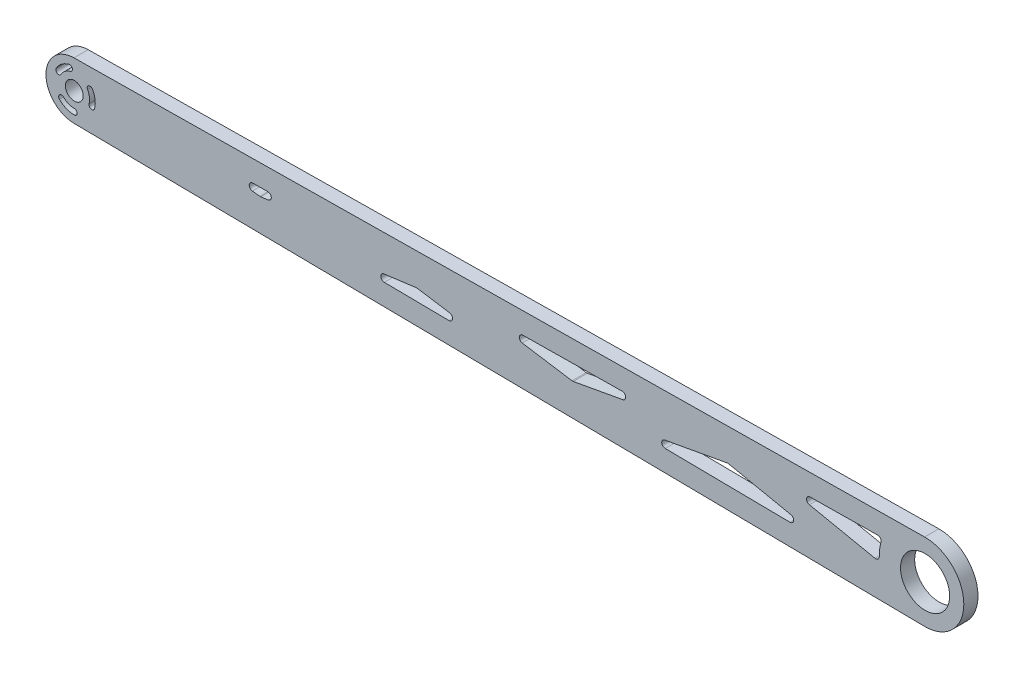
SolidWorks part; units mm, degrees
ref_plane "Front Plane" through (0, 0, 0) normal (0, 0, 1) x (1, 0, 0)
ref_plane "Top Plane" through (0, 0, 0) normal (0, 1, 0) x (1, 0, 0)
ref_plane "Right Plane" through (0, 0, 0) normal (1, 0, 0) x (0, 0, -1)
sketch "Sketch1" plane through (0, 0, 0) normal (0, 0, 1) x (1, 0, 0)
  line L0 (0, 0) -> (381, 0) construction
  line L4 (-0.155, 12.6991) -> (380.7882, 17.3487)
  line L5 (-0.155, -12.6991) -> (380.7882, -17.3487)
  circle A0 centre (0, 0) radius 4
  arc A1 (-0.155, 12.6991) -> (-0.155, -12.6991) centre (0, 0) ccw
  circle A2 centre (0, 0) radius 12.7 construction
  arc A5 (380.7882, -17.3487) -> (380.7882, 17.3487) centre (381, 0) ccw
  circle A6 centre (381, 0) radius 11
  dimension "D1" = 8
  dimension "D2" = 12.7
  dimension "D6" = 22
  dimension "D7" = 6.35
  dimension "D5" = 381
extrude "Boss-Extrude1" add sketch "Sketch1" along normal blind 6.35 contours A1 A5 A0 region at (198.4687, 0, 0)
sketch "Sketch2" plane through (0, 0, 6.35) normal (0, 0, 1) x (1, 0, 0)
  line L4 (13.1073, 3.3352) -> (83.3647, -4.1928) construction
  line L5 (13.6147, 8.0706) -> (83.8721, 0.5426)
  line L6 (-0.0387, -3.1748) -> (380.9045, -7.8244)
  line L7 (380.9045, 7.8244) -> (-0.0388, 3.1748)
  line L8 (-0.0387, -3.1748) -> (380.9045, -7.8244)
  line L9 (380.9045, 7.8244) -> (-0.0388, 3.1748)
  line L10 (12.5999, -1.4002) -> (82.8573, -8.9282)
  line L11 (83.3647, -4.1928) -> (153.4175, 5.0478) construction
  line L12 (82.7419, 0.5288) -> (152.7947, 9.7694)
  line L13 (83.9876, -8.9144) -> (154.0403, 0.3262)
  line L14 (153.4175, 5.0478) -> (223.2238, -5.8998) construction
  line L15 (154.1554, 9.7528) -> (223.9617, -1.1948)
  line L16 (152.6796, 0.3428) -> (222.4859, -10.6048)
  line L17 (223.2238, -5.8998) -> (292.7421, 6.7483) construction
  line L18 (222.3713, -1.2142) -> (291.8897, 11.4339)
  line L19 (224.0763, -10.5854) -> (293.5946, 2.0628)
  line L20 (292.7421, 6.7483) -> (361.9311, -7.5928) construction
  line L21 (293.7088, 11.4117) -> (362.8977, -2.9295)
  line L22 (291.7755, 2.085) -> (360.9645, -12.2562)
  circle A5 centre (381, 0) radius 11 construction
  arc A6 (380.9045, -7.8244) -> (380.9045, 7.8244) centre (381, 0) ccw
  arc A7 (-0.0388, 3.1748) -> (-0.0387, -3.1748) centre (0, 0) ccw
  arc A8 (380.9045, -7.8244) -> (380.9045, 7.8244) centre (381, 0) ccw
  arc A9 (-0.0388, 3.1748) -> (-0.0387, -3.1748) centre (0, 0) ccw
  circle A10 centre (0, 0) radius 13.525
  circle A11 centre (0, 0) radius 13.525
  circle A12 centre (381, 0) radius 11 construction
  circle A13 centre (381, 0) radius 20.525
  arc A14 (13.6147, 8.0706) -> (12.5999, -1.4002) centre (13.1073, 3.3352) ccw
  arc A15 (82.8573, -8.9282) -> (83.8721, 0.5426) centre (83.3647, -4.1928) ccw
  arc A16 (82.7419, 0.5288) -> (83.9876, -8.9144) centre (83.3647, -4.1928) ccw
  arc A17 (154.0403, 0.3262) -> (152.7947, 9.7694) centre (153.4175, 5.0478) ccw
  arc A18 (154.1554, 9.7528) -> (152.6796, 0.3428) centre (153.4175, 5.0478) ccw
  arc A19 (222.4859, -10.6048) -> (223.9617, -1.1948) centre (223.2238, -5.8998) ccw
  arc A20 (222.3713, -1.2142) -> (224.0763, -10.5854) centre (223.2238, -5.8998) ccw
  arc A21 (293.5946, 2.0628) -> (291.8897, 11.4339) centre (292.7421, 6.7483) ccw
  arc A22 (293.7088, 11.4117) -> (291.7755, 2.085) centre (292.7421, 6.7483) ccw
  arc A23 (360.9645, -12.2562) -> (362.8977, -2.9295) centre (361.9311, -7.5928) ccw
  point P9 (48.236, -0.4288)
  point P14 (118.3911, 0.4275)
  point P27 (188.3206, -0.426)
  point P36 (257.983, 0.4243)
  point P41 (327.3366, -0.4222)
  point P48 (0, 0)
  point P49 (0, 0)
  dimension "D4" = 4.7625
  dimension "D1" = 9.525
  dimension "D2" = 9.525
  dimension "D3" = 9.525
extrude "Cut-Extrude1" cut sketch "Sketch2" against normal through all contours L5 L12 L9 | L16 L13 L8 | L15 L18 L9 | L22 L19 L8 | A13 L9 L21 region at (83.277, 2.9954, 6.35) region at (153.3158, -3.2854, 6.35) region at (223.1082, 3.5754, 6.35) region at (292.6126, -3.8653, 6.35) region at (345.5359, 4.0782, 6.35)
fillet "Fillet2" radius 1.5875 15 edges at (336.9978, -7.2885, 3.175) (248.1571, -6.2042, 3.175) (292.6829, 1.8969, 3.175) (189.8908, -5.493, 3.175) (116.6977, -4.5996, 3.175) (153.3588, 0.2363, 3.175) (264.223, 6.4002, 3.175) (223.1649, -1.0699, 3.175) (181.9367, 5.3959, 3.175) (314.9023, 7.0188, 3.175) (361.9311, 7.5928, 3.175) (113.2868, 4.558, 3.175) (83.3062, 0.6033, 3.175) (53.238, 3.825, 3.175) (360.6227, -2.4579, 3.175)
sketch "Sketch3" plane through (0, 0, 6.35) normal (0, 0, 1) x (1, 0, 0)
  line L0 (0, 0) -> (0, -8.1175) construction
  line L1 (0, 0) -> (-5.7399, -5.7399) construction
  arc A0 (0, -8.1175) -> (-5.7399, -5.7399) centre (0, 0) cw construction
  arc A1 (-6.638, -6.638) -> (0, -9.3875) centre (0, 0) ccw
  arc A2 (-4.8419, -4.8419) -> (0, -6.8475) centre (0, 0) ccw
  arc A3 (-4.8419, -4.8419) -> (-6.638, -6.638) centre (-5.7399, -5.7399) ccw
  arc A4 (0, -9.3875) -> (0, -6.8475) centre (0, -8.1175) ccw
  arc A5 (-7.03, 4.0587) -> (-2.101, 7.8409) centre (0, 0) cw construction
  arc A6 (-2.4297, 9.0676) -> (-8.1298, 4.6937) centre (0, 0) ccw
  arc A7 (-1.7723, 6.6142) -> (-5.9301, 3.4237) centre (0, 0) ccw
  arc A8 (-1.7723, 6.6142) -> (-2.4297, 9.0676) centre (-2.101, 7.8409) ccw
  arc A9 (-8.1298, 4.6937) -> (-5.9301, 3.4237) centre (-7.03, 4.0587) ccw
  arc A10 (7.03, 4.0587) -> (7.8409, -2.101) centre (0, 0) cw construction
  arc A11 (9.0676, -2.4297) -> (8.1298, 4.6937) centre (0, 0) ccw
  arc A12 (6.6142, -1.7723) -> (5.9301, 3.4237) centre (0, 0) ccw
  arc A13 (6.6142, -1.7723) -> (9.0676, -2.4297) centre (7.8409, -2.101) ccw
  arc A14 (8.1298, 4.6937) -> (5.9301, 3.4237) centre (7.03, 4.0587) ccw
  point P4 (-3.1064, -7.4996)
  point P13 (-4.9416, 6.44)
  point P20 (8.0481, 1.0595)
  point P25 (0, 0)
  dimension "D1" = 8.1175
  dimension "D2" = 1.27
  dimension "D4" = 45
  dimension "D3" = 3
extrude "Cut-Extrude2" cut sketch "Sketch3" against normal through all both and the other way through all
